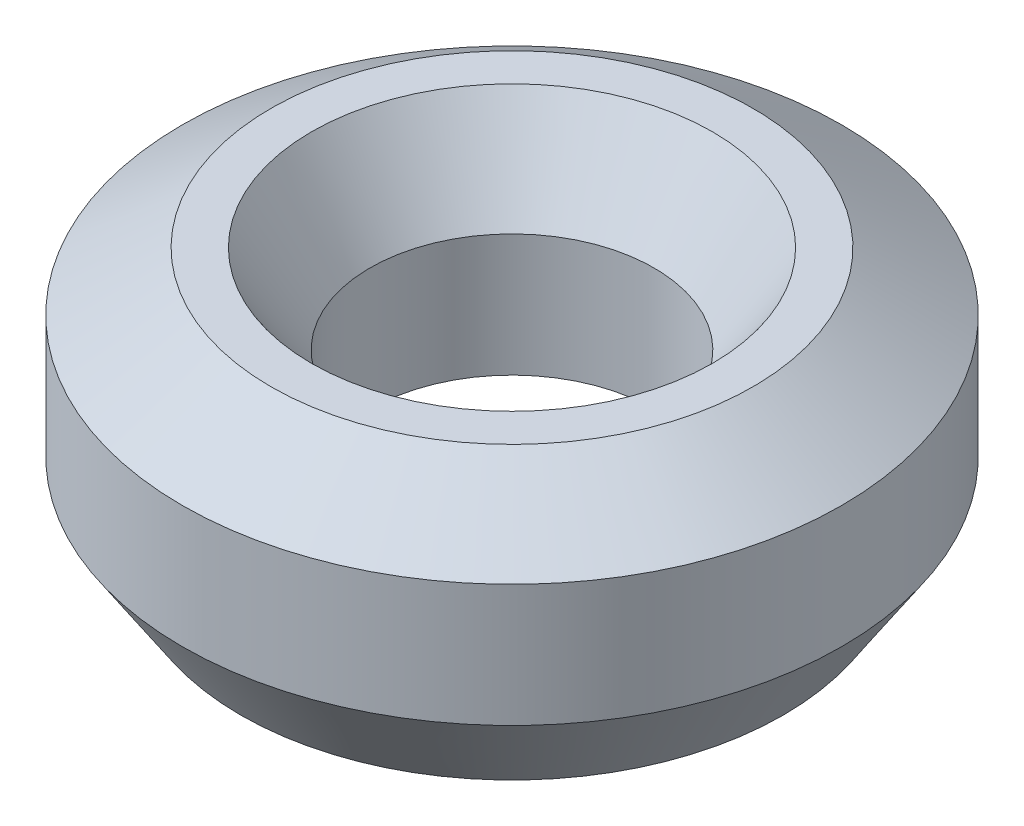
SolidWorks part; units mm, degrees
ref_plane "Front Plane" through (0, 0, 0) normal (0, 0, 1) x (1, 0, 0)
ref_plane "Top Plane" through (0, 0, 0) normal (0, 1, 0) x (1, 0, 0)
ref_plane "Right Plane" through (0, 0, 0) normal (1, 0, 0) x (0, 0, -1)
sketch "Sketch1" plane through (0, 0, 0) normal (0, 1, 0) x (1, 0, 0)
  circle A0 centre (0, 0) radius 22.5
  dimension "SLEEVE_OD" = 45
extrude "Boss-Extrude1" add sketch "Sketch1" along normal blind 18.3851
sketch "Sketch2" plane through (0, 0, 0) normal (0, 1, 0) x (1, 0, 0)
  circle A0 centre (0, 0) radius 9.6934
  dimension "BORE_D" = 19.3867
extrude "Cut-Extrude1" cut sketch "Sketch2" along normal through all
chamfer "Chamfer1" distance 3.993 angle 56.563 4 edges at (0, 18.3851, 9.6934) (0, 0, 9.6934) (0, 0, 22.5) (0, 18.3851, 22.5) first distance on face at (0, 18.3851, 9.6934) first distance on face at (0, 0, 9.6934) first distance on face at (0, 18.3851, 22.5)
